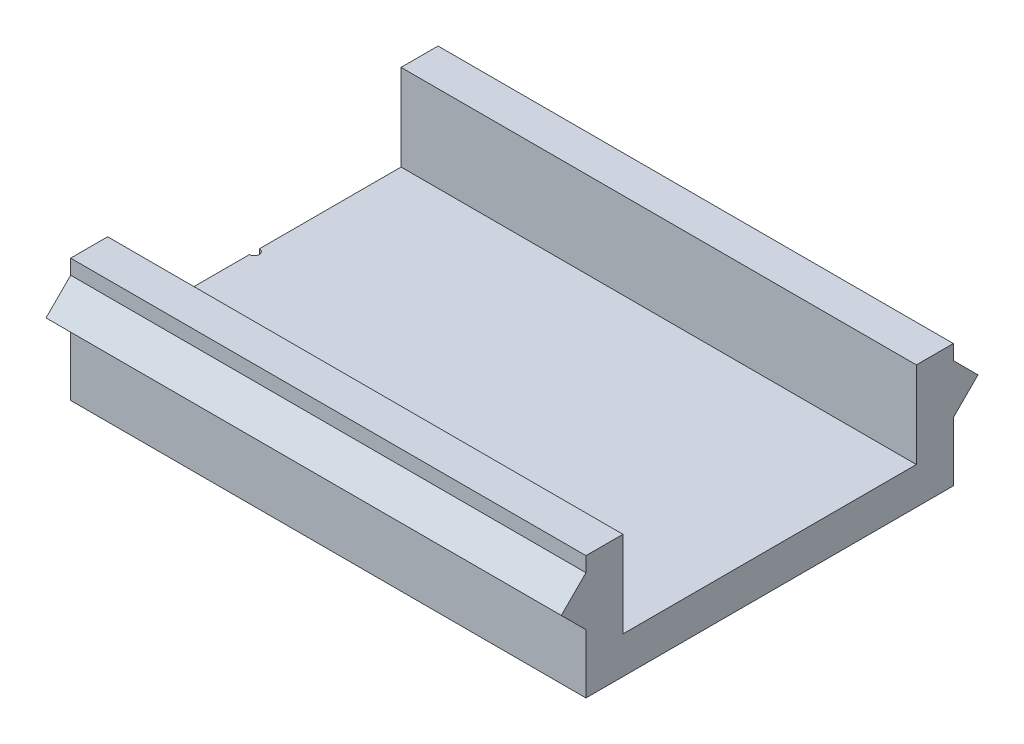
SolidWorks part; units mm, degrees
ref_plane "Спереди" through (0, 0, 0) normal (0, 0, 1) x (1, 0, 0)
ref_plane "Сверху" through (0, 0, 0) normal (0, 1, 0) x (1, 0, 0)
ref_plane "Справа" through (0, 0, 0) normal (1, 0, 0) x (0, 0, -1)
sketch "Sketch2" plane through (0, 0, 0) normal (0, 1, 0) x (1, 0, 0)
  line L0 (-20.9, 0.4) -> (-20.9, 14.9)
  line L1 (-20.9, -14.9) -> (20.9, -14.9)
  line L2 (-20.9, -14.9) -> (-20.9, -0.4)
  line L3 (-20.9, 14.9) -> (20.9, 14.9)
  line L4 (20.9, -14.9) -> (20.9, 14.9)
  line L5 (-20.9, -14.9) -> (20.9, 14.9) construction
  line L6 (-20.9, 14.9) -> (20.9, -14.9) construction
  line L7 (-20.9, 14.9) -> (-20.9, -14.9) construction
  arc A0 (-20.9, -0.4) -> (-20.9, 0.4) centre (-20.9, 0) ccw
  point P0 (0, 0)
  point P7 (0, 0)
  point P10 (0, 0)
  point P11 (-20.9, -1.1852)
  point P12 (0, 0)
  point P13 (-20.9, -0.4634)
  point P14 (-20.9, -0.167)
  point P15 (-20.9, 0)
  dimension "D3" = 0.4
  dimension "D1" = 41.8
  dimension "D2" = 29.8
extrude "Boss-Extrude1" add sketch "Sketch2" along normal blind 3 contours L2 A0 L0 L3 L4 L1
sketch "Sketch4" plane through (-20.9, 0, 0) normal (-1, 0, 0) x (0, 0, 1)
  line L0 (-14.9, 3) -> (-14.9, 4.8)
  line L1 (-14.9, 4.8) -> (-16.9, 6.8)
  line L2 (-16.9, 6.8) -> (-14.9, 8.8)
  line L3 (-14.9, 8.8) -> (-14.9, 10)
  line L4 (-14.9, 10) -> (-11.9, 10)
  line L5 (-11.9, 10) -> (-11.9, 3)
  line L6 (14.9, 3) -> (0.4, 3) construction
  line L7 (0, 0) -> (0, 22.6198) construction
  line L8 (-14.9, 3) -> (-11.9, 3)
  line L9 (14.9, 0) -> (0.4, 0) construction
  line L10 (14.9, 3) -> (11.9, 3)
  line L11 (11.9, 10) -> (11.9, 3)
  line L12 (14.9, 10) -> (11.9, 10)
  line L13 (14.9, 8.8) -> (14.9, 10)
  line L14 (16.9, 6.8) -> (14.9, 8.8)
  line L15 (14.9, 4.8) -> (16.9, 6.8)
  line L16 (14.9, 3) -> (14.9, 4.8)
  line L17 (-0.4, 3) -> (0.4, 3) construction
  line L18 (-0.4, 3) -> (-14.9, 3) construction
  point P15 (0, 0)
  point P27 (0, 3)
  point P28 (-12.483, 3)
  point P32 (0, 0)
  dimension "D1" = 2
  dimension "D2" = 45
  dimension "D3" = 10
  dimension "D4" = 1.2
  dimension "D5" = 3
extrude "Boss-Extrude2" add sketch "Sketch4" against normal up to surface (41.8 mm away) up to face at (20.9, 1.5, 0)
sketch "Sketch5" plane through (0, 0, 0) normal (0, -1, 0) x (1, 0, 0)
  circle A0 centre (0, 0) radius 2.6
  dimension "D1" = 5.2
extrude "Cut-Extrude1" cut sketch "Sketch5" against normal blind 0.6
